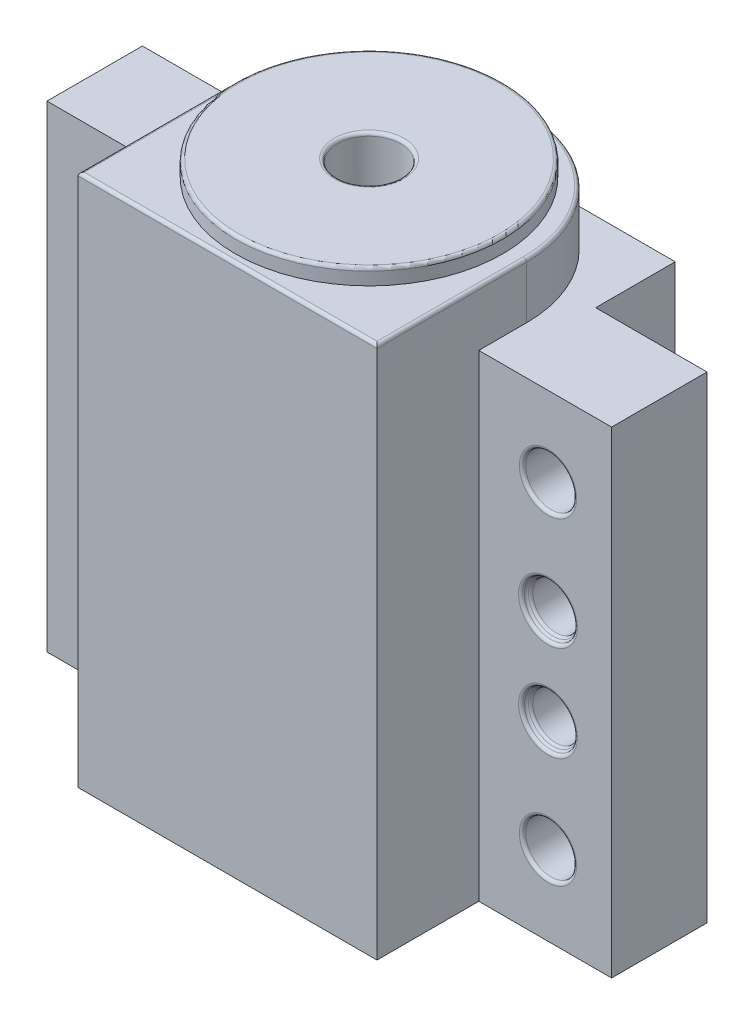
SolidWorks part; units mm, degrees
ref_plane "Front Plane" through (0, 0, 0) normal (0, 0, 1) x (1, 0, 0)
ref_plane "Top Plane" through (0, 0, 0) normal (0, 1, 0) x (1, 0, 0)
ref_plane "Right Plane" through (0, 0, 0) normal (1, 0, 0) x (0, 0, -1)
sketch "Main1" plane through (0, 0, 0) normal (0, 0, 1) x (1, 0, 0)
  line L1 (0, 0) -> (35.5, 0)
  line L2 (0, 0) -> (0, 30)
  line L3 (0, 30) -> (35.5, 30)
  line L4 (35.5, 0) -> (35.5, 30)
  dimension "D1" = 35.5
  dimension "D2" = 30
extrude "Main" add sketch "Main1" along normal blind 11 contours L3 L4 L1 L2
sketch "Sketch3" plane through (0, 0, 0) normal (0, 0, -1) x (-1, 0, 0)
  line L0 (-31.5, 30) -> (-31.5, 0) construction
  line L1 (0, 30) -> (-35.5, 30) construction
  line L2 (0, 0) -> (-35.5, 0) construction
  line L3 (-31.5, 15) -> (-17.75, 15) construction
  line L4 (-17.75, 15) -> (-17.75, 30) construction
  line L5 (-17.75, 15) -> (-4, 15) construction
  line L6 (-4, 30) -> (-4, 0) construction
  circle A0 centre (-31.5, 25) radius 1.6
  circle A1 centre (-31.5, 5) radius 1.6
  circle A2 centre (-4, 5) radius 1.6
  circle A3 centre (-4, 25) radius 1.6
  dimension "D2" = 3.2
  dimension "D1" = 27.5
  dimension "D3" = 5
  dimension "D4" = 5
extrude "Cut-Extrude1" cut sketch "Sketch3" against normal up to next
sketch "Adjustable Standoff Heat Sets" plane through (0, 0, 11) normal (0, 0, 1) x (1, 0, 0)
  line L0 (4, 25) -> (4, 5) construction
  line L1 (17.75, 30) -> (17.75, 0) construction
  line L2 (0, 30) -> (35.5, 30) construction
  line L3 (0, 0) -> (35.5, 0) construction
  point P10 (4, 18)
  point P11 (4, 12)
  point P12 (31.5, 12)
  point P13 (31.5, 18)
  dimension "D1" = 7
  dimension "D2" = 7
hole_wizard "M2 Heat Sets" positions "3DSketch1" profile "Sketch6" counterbore size "M72" standard "ANSI Metric"
sketch3d "3DSketch1"
  point P0 (4, 18, 11)
  point P3 (4, 12, 11)
  point P6 (31.5, 18, 11)
  point P9 (31.5, 12, 11)
sketch "Sketch6" plane through (4, 18, 11) normal (1, 0, 0) x (0, -1, 0)
  line L0 (0, 0) -> (0, 6)
  line L1 (0, 6) -> (1.45, 6)
  line L2 (1.45, 6) -> (1.45, 0.3)
  line L3 (1.45, 0.3) -> (1.65, 0.3)
  line L4 (1.65, 0.3) -> (1.65, 0)
  line L5 (1.65, 0) -> (0, 0)
  line L10 (0, 6) -> (-1.45, 6) construction
  line L11 (0, -6.35) -> (0, 107.95) construction
  dimension "Hole Dia." = 2.9
  dimension "Hole Depth" = 6
  dimension "C'Bore Dia." = 3.3
  dimension "C'Bore Depth" = 0.3
  dimension "Drill Angle" = 180
sketch "Sketch7" plane through (0, 0, 0) normal (0, 0, -1) x (-1, 0, 0)
  line L0 (-31.5, 28) -> (-35.5, 28) construction
  line L1 (-35.5, 0) -> (-35.5, 30) construction
  line L2 (-28.5, 25) -> (-28.5, 5) construction
  line L3 (-31.5, 2) -> (-35.5, 2) construction
  line L4 (-35.5, 28) -> (-35.5, 2) construction
  line L5 (-17.75, 30) -> (-17.75, 0) construction
  line L6 (0, 30) -> (-35.5, 30) construction
  line L7 (0, 0) -> (-35.5, 0) construction
  line L8 (-4, 2) -> (0, 2) construction
  line L9 (0, 28) -> (0, 2) construction
  line L10 (-4, 28) -> (0, 28) construction
  line L11 (-7, 25) -> (-7, 5) construction
  line L12 (0, 0) -> (-7, 0)
  line L13 (-35.5, 30) -> (-28.5, 30)
  line L14 (-35.5, 30) -> (-35.5, 0)
  line L15 (-35.5, 0) -> (-28.5, 0)
  line L16 (-28.5, 30) -> (-28.5, 0)
  line L17 (-7, 30) -> (-7, 0)
  line L18 (0, 30) -> (-7, 30)
  line L19 (0, 30) -> (0, 0)
  arc A0 (-28.5, 25) -> (-31.5, 28) centre (-31.5, 25) ccw construction
  arc A1 (-31.5, 2) -> (-28.5, 5) centre (-31.5, 5) ccw
  circle A2 centre (-4, 25) radius 3 construction
  circle A3 centre (-4, 5) radius 3 construction
  arc A4 (-31.5, 28) -> (-28.5, 25) centre (-31.5, 25) ccw construction
  arc A5 (-28.5, 5) -> (-31.5, 2) centre (-31.5, 5) ccw construction
  arc A6 (-7, 25) -> (-4, 28) centre (-4, 25) cw construction
  arc A7 (-4, 2) -> (-7, 5) centre (-4, 5) cw construction
  circle M10 centre (-4, 25) radius 1.6
  circle M11 centre (-4, 5) radius 1.6
  circle M12 centre (-31.5, 5) radius 1.6
  circle M13 centre (-31.5, 25) radius 1.6
  line M14 (0, 0) -> (0, 30)
  line M15 (0, 30) -> (-35.5, 30)
  line M16 (-35.5, 30) -> (-35.5, 0)
  line M17 (-35.5, 0) -> (0, 0)
  dimension "D1" = 6
extrude "Countersink" cut sketch "Sketch7" against normal blind 5 contours L16 M15 M16 M17 M13 M12 | L17 M15 M17 M14 M10 M11 region at (3.4585, 15, 0) region at (32.0415, 15, 0)
sketch "Sketch8" plane through (0, 0, 11) normal (0, 0, 1) x (1, 0, 0)
  line L0 (0, 30) -> (35.5, 30) construction
  line L1 (8.35, 30) -> (27.15, 30)
  line L2 (8.35, 30) -> (8.35, 0)
  line L3 (8.35, 0) -> (27.15, 0)
  line L4 (27.15, 30) -> (27.15, 0)
  line L5 (8.35, 30) -> (0, 30) construction
  line L6 (27.15, 30) -> (35.5, 30) construction
  line L7 (0, 0) -> (35.5, 0) construction
  dimension "D1" = 18.8
extrude "Motor Hold" add sketch "Sketch8" along normal blind 6.4
sketch "Sketch9" plane through (0, 0, 0) normal (0, 0, -1) x (-1, 0, 0)
  line L0 (-7, 30) -> (-28.5, 30) construction
  line L1 (-23.75, 30) -> (-11.75, 30)
  line L2 (-23.75, 30) -> (-23.75, 23)
  line L3 (-23.75, 23) -> (-11.75, 23)
  line L4 (-11.75, 30) -> (-11.75, 23)
  line L5 (-23.75, 26.5) -> (-28.5, 26.5) construction
  line L6 (-28.5, 30) -> (-28.5, 0) construction
  line L7 (-11.75, 26.5) -> (-7, 26.5) construction
  line L8 (-7, 30) -> (-7, 0) construction
  line L11 (-25.25, 11.5) -> (-28.5, 11.5) construction
  line L12 (-25.25, 23) -> (-10.25, 23)
  line L13 (-25.25, 23) -> (-25.25, 0)
  line L14 (-25.25, 0) -> (-10.25, 0)
  line L15 (-10.25, 23) -> (-10.25, 0)
  line L16 (-10.25, 11.5) -> (-7, 11.5) construction
  line L17 (-7, 0) -> (-28.5, 0) construction
  line M11 (-7, 30) -> (-28.5, 30)
  line M13 (-28.5, 0) -> (-7, 0)
  dimension "D1" = 12
  dimension "D2" = 7
  dimension "D3" = 15
extrude "Motor Clearance" cut sketch "Sketch9" against normal blind 13.6 contours L15 L12 L3 L13 M13 | L4 L2 L3 M11 region at (17.75, 26.5, 0) region at (17.75, 11.5, 0)
sketch "Motor Mount Plate" plane through (0, 30, 0) normal (0, 1, 0) x (1, 0, 0)
  line L0 (27.15, -17.4) -> (27.15, 0) construction
  line L1 (8.35, -17.4) -> (27.15, -17.4)
  line L2 (8.35, -17.4) -> (8.35, 0)
  line L3 (8.35, 0) -> (27.15, 0)
  line L4 (27.15, -17.4) -> (27.15, 0)
  line L6 (7, 0) -> (11.75, 0) construction
extrude "Motor Mount" add sketch "Motor Mount Plate" along normal blind 3.5
sketch "Sketch12" plane through (0, 30, 0) normal (0, -1, 0) x (1, 0, 0)
  line L0 (17.75, 13.6) -> (17.75, 8.5) construction
  line L1 (11.75, 13.6) -> (23.75, 13.6) construction
  line L2 (17.75, 8.5) -> (22.25, 8.5) construction
  line L3 (17.75, 8.5) -> (13.25, 8.5) construction
  circle A2 centre (17.75, 8.5) radius 2
  dimension "D4" = 4
  dimension "D1" = 5.1
  dimension "D2" = 9
extrude "Mount Holes" cut sketch "Sketch12" against normal up to next
sketch "Sketch14" plane through (0, 23, 0) normal (0, -1, 0) x (1, 0, 0)
  line L0 (28.5, 5) -> (28.5, 0) construction
  line L1 (7, 0) -> (28.5, 0)
  line L2 (7, 0) -> (7, 3.6)
  line L3 (7, 3.6) -> (28.5, 3.6)
  line L4 (28.5, 0) -> (28.5, 3.6)
  line L5 (11.75, 13.6) -> (23.75, 13.6) construction
  dimension "D1" = 10
extrude "Top" add sketch "Sketch14" against normal up to surface (7 mm away) up to face at (17.75, 30, 6.5)
sketch "Sketch15" plane through (0, 33.5, 0) normal (0, 1, 0) x (1, 0, 0)
  circle A0 centre (17.75, -8.5) radius 8.4
  circle A3 centre (17.75, -8.5) radius 2 construction
  circle A4 centre (17.75, -8.5) radius 2
  dimension "D1" = 16.8
extrude "Anti-Rub Spacer" add sketch "Sketch15" along normal blind 1
fillet "Fillet2" radius 8 2 edges at (27.15, 31.75, 0) (8.35, 31.75, 0)
ref_plane "Plane1" through (0, 34.5, 0) normal (0, 1, 0) x (1, 0, 0)
fillet "Fillet6" radius 0.2 2 edges at (32.95, 12, 5) (33.15, 12, 11)
fillet "Fillet7" radius 0.2 1 edges at (32.95, 12, 10.7)
fillet "Fillet8" radius 0.2 9 edges at (33.15, 12, 10.7) (10.6931, 33.5, 2.3431) (24.8069, 33.5, 2.3431) (17.75, 34.5, 16.9) (17.75, 33.5, 0) (8.35, 33.5, 12.7) (17.75, 33.5, 17.4) (27.15, 33.5, 12.7) (17.75, 34.5, 10.5)
fillet "Fillet10" radius 0.2 1 edges at (5.45, 18, 10.7)
fillet "Fillet11" radius 0.2 3 edges at (5.65, 18, 10.7) (5.45, 12, 5) (5.65, 12, 11)
fillet "Fillet12" radius 0.2 1 edges at (5.45, 12, 10.7)
fillet "Fillet13" radius 0.2 3 edges at (5.65, 12, 10.7) (32.95, 18, 5) (33.15, 18, 11)
fillet "Fillet14" radius 0.2 1 edges at (32.95, 18, 10.7)
fillet "Fillet15" radius 0.2 1 edges at (33.15, 18, 10.7)
fillet "Fillet16" radius 0.2 4 edges at (2.4, 25, 11) (2.4, 5, 11) (29.9, 5, 11) (29.9, 25, 11)
chamfer "Chamfer1" distance 1.7 angle 40 4 edges at (29.9, 25, 5) (2.4, 5, 5) (2.4, 25, 5) (29.9, 5, 5) first distance on face at (29.9, 25, 10.8) first distance on face at (2.4, 5, 10.8) first distance on face at (2.4, 25, 10.8) first distance on face at (29.9, 5, 10.8)
sketch "Sketch17" plane through (0, 0, 13.6) normal (0, 0, -1) x (-1, 0, 0)
  line L0 (-25.25, 0) -> (-10.25, 0) construction
  line L1 (-25.25, 23) -> (-23.8, 23)
  line L2 (-25.25, 23) -> (-25.25, 0)
  line L3 (-25.25, 0) -> (-23.8, 0)
  line L4 (-23.8, 23) -> (-23.8, 0)
  line L6 (-10.25, 23) -> (-11.7, 23)
  line L7 (-10.25, 23) -> (-10.25, 0)
  line L8 (-10.25, 0) -> (-11.7, 0)
  line L9 (-11.7, 23) -> (-11.7, 0)
  dimension "D1" = 12.1
extrude "Boss-Extrude1" add sketch "Sketch17" along normal blind 10
chamfer "Chamfer2" distance 1.5 angle 45 2 edges at (23.8, 11.5, 3.6) (11.7, 11.5, 3.6)
